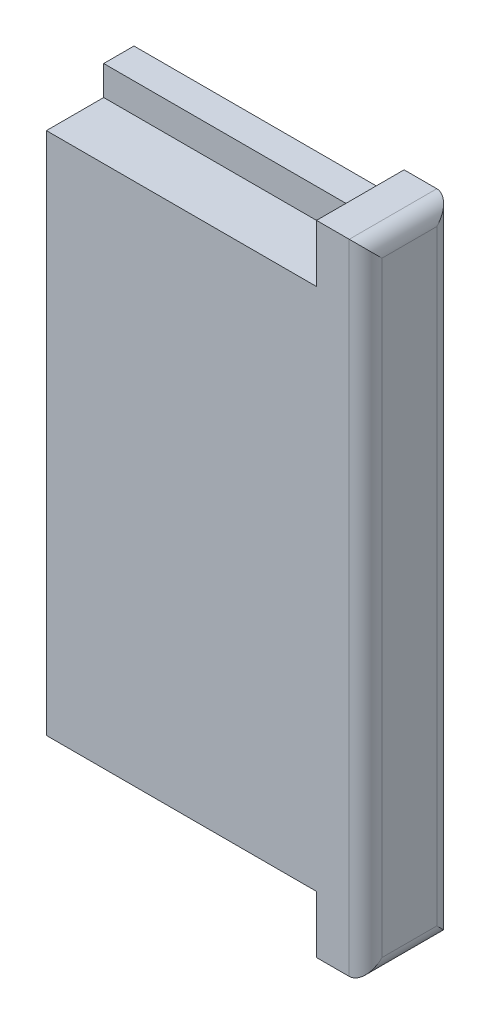
SolidWorks part; units mm, degrees
ref_plane "Piano frontale" through (0, 0, 0) normal (0, 0, 1) x (1, 0, 0)
ref_plane "Piano superiore" through (0, 0, 0) normal (0, 1, 0) x (1, 0, 0)
ref_plane "Piano destro" through (0, 0, 0) normal (1, 0, 0) x (0, 0, -1)
sketch "Sketch1" plane through (0, 0, 0) normal (0, 0, 1) x (1, 0, 0)
  line L0 (-8.25, 17.8) -> (8.25, -17.8) construction
  line L1 (-8.25, 17.8) -> (8.25, 17.8)
  line L2 (-8.25, 17.8) -> (-8.25, -17.8)
  line L3 (-8.25, -17.8) -> (8.25, -17.8)
  line L4 (8.25, 17.8) -> (8.25, -17.8)
  point P4 (0, 0)
  dimension "D1" = 35.6
  dimension "D2" = 16.5
extrude "Int" add sketch "Sketch1" along normal blind 1.85
sketch "Sketch2" plane through (0, 0, 1.85) normal (0, 0, 1) x (1, 0, 0)
  line L0 (8.25, -17.8) -> (8.25, 17.8) construction
  line L1 (8.25, 16) -> (-8.25, 16)
  line L2 (8.25, 16) -> (8.25, -16)
  line L3 (8.25, -16) -> (-8.25, -16)
  line L4 (-8.25, 16) -> (-8.25, -16)
  line L5 (8.25, 17.8) -> (-8.25, 17.8) construction
  line L6 (-8.25, -17.8) -> (8.25, -17.8) construction
  line L7 (-8.25, 17.8) -> (-8.25, -17.8) construction
  dimension "D1" = 1.8
  dimension "D2" = 1.8
extrude "Ext" add sketch "Sketch2" along normal blind 3.5
sketch "Sketch3" plane through (8.25, 0, 0) normal (1, 0, 0) x (0, 0, -1)
  line L0 (0, -17.8) -> (0, 17.8) construction
  line L1 (0, 19.5) -> (-5.35, 19.5)
  line L2 (0, 19.5) -> (0, -19.5)
  line L3 (0, -19.5) -> (-5.35, -19.5)
  line L4 (-5.35, 19.5) -> (-5.35, -19.5)
  line L5 (-5.35, -16) -> (-5.35, 16) construction
  line L6 (0, 0) -> (-5.35, 0) construction
  point P12 (-5.35, 0)
  dimension "D1" = 39
extrude "Top" add sketch "Sketch3" along normal blind 3
fillet "Fillet1" radius 1 4 edges at (11.25, -19.5, 2.675) (11.25, 0, 5.35) (11.25, 19.5, 2.675) (11.25, 0, 0)
